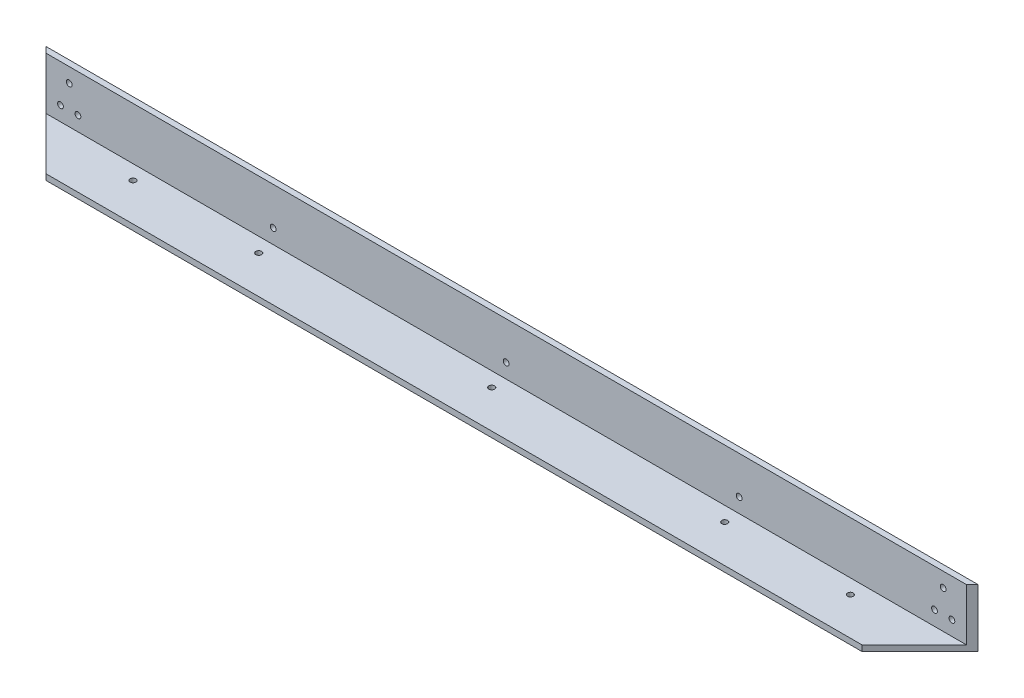
SolidWorks part; units mm, degrees
ref_plane "Front Plane" through (0, 0, 0) normal (0, 0, 1) x (1, 0, 0)
ref_plane "Top Plane" through (0, 0, 0) normal (0, 1, 0) x (1, 0, 0)
ref_plane "Right Plane" through (0, 0, 0) normal (1, 0, 0) x (0, 0, -1)
sketch "Sketch1" plane through (0, 0, 0) normal (1, 0, 0) x (0, 0, -1)
  line L0 (0, 0) -> (-31.75, 0)
  line L1 (-31.75, 0) -> (-31.75, 3.175)
  line L2 (-31.75, 3.175) -> (-3.175, 3.175)
  line L3 (-3.175, 3.175) -> (-3.175, 31.75)
  line L4 (-3.175, 31.75) -> (0, 31.75)
  line L5 (0, 31.75) -> (0, 0)
  dimension "LHeight" = 31.75
  dimension "LWidth" = 31.75
  dimension "LMaterialThickness" = 3.175
  dimension "D1" = 28.575
  dimension "D2" = 28.575
  dimension "D3" = 3.175
extrude "Boss-Extrude1" add sketch "Sketch1" along normal blind 510
chamfer "Chamfer6" distance 31.75 angle 45 1 edges at (510, 1.5875, 31.75)
chamfer "Chamfer7" distance 31.75 angle 45 1 edges at (0, 1.5875, 31.75)
sketch "TopHoles-Sketch3" plane through (0, 3.175, 0) normal (0, 1, 0) x (1, 0, 0)
  line L0 (510, 0) -> (0, 0) construction
  circle A9 centre (451.2625, -11.1125) radius 1.5875
  circle A10 centre (58.7375, -11.1125) radius 1.5875
  circle A13 centre (127.5, -11.1125) radius 1.5875
  circle A14 centre (255, -11.1125) radius 1.5875
  circle A15 centre (382.5, -11.1125) radius 1.5875
  dimension "D10" = 127.5
  dimension "D5" = 3.175
  dimension "D11" = 127.5
  dimension "D13" = 127.5
  dimension "D2" = 11.1125
  dimension "D3" = 58.7375
  dimension "D4" = 58.7375
extrude "TopHoles-Cut-Extrude2" cut sketch "TopHoles-Sketch3" against normal through all
sketch "FrontHoles-Sketch4" plane through (0, 0, 3.175) normal (0, 0, 1) x (1, 0, 0)
  line L0 (0, 0) -> (0, 31.75) construction
  line L1 (510, 0) -> (510, 31.75) construction
  line L3 (510, 31.75) -> (0, 31.75) construction
  line L7 (510, 0) -> (0, 0) construction
  circle A3 centre (494.125, 23.8125) radius 1.5875
  circle A4 centre (15.875, 23.8125) radius 1.5875
  circle A6 centre (11.1125, 11.1125) radius 1.5875
  circle A7 centre (20.6375, 11.1125) radius 1.5875
  circle A8 centre (489.3625, 11.1125) radius 1.5875
  circle A9 centre (498.8875, 11.1125) radius 1.5875
  circle A10 centre (127.5, 11.1125) radius 1.5875
  circle A11 centre (255, 11.1125) radius 1.5875
  circle A12 centre (382.5, 11.1125) radius 1.5875
  dimension "D2" = 3.175
  dimension "D7" = 11.1125
  dimension "D6" = 15.875
  dimension "D5" = 15.875
  dimension "D8" = 127.5
  dimension "D9" = 127.5
  dimension "D10" = 127.5
  dimension "D4" = 7.9375
  dimension "D11" = 11.1125
  dimension "D3" = 11.1125
  dimension "D12" = 20.6375
  dimension "D13" = 20.6375
extrude "FrontHoles-Cut-Extrude3" cut sketch "FrontHoles-Sketch4" against normal through all
equation "\"TopRailWidth\"= 1.25in"
equation "\"TopRailHeight\"= 1.25in"
equation "\"RailThickness\"= .125in'Spec"
equation "\"SideRailHoleY1FromEdge\"= \"HoleOffsetFromEdge\""
equation "\"SideRailHoleX1FromSide\"= \"HoleOffsetFromSide\""
equation "\"FrontBackRailLength\"= 510mm"
equation "\"VSWidth\"= 1.25in'Spec"
equation "\"HoleOffsetFromEdge\"= \"RailThickness\" * 2.5"
equation "\"HoleOffsetFromSide\"= \"RailThickness\" * 3.5"
equation "\"SideRailHoleX2FromSide\"= \"VSWidth\" - \"HoleOffsetFromEdge\" - \"RailThickness\"'Equals 20.6375"
equation "\"FasteningHoleDiameter\"= .125in"
equation "\"SideRailHoleY2FromSide\"= \"HoleOffsetFromSide\""
equation "\"LWidth@Sketch1\"=\"TopRailWidth\""
equation "\"LHeight@Sketch1\"=\"TopRailHeight\""
equation "\"LMaterialThickness@Sketch1\"=\"RailThickness\""
equation "\"D1@Boss-Extrude1\"= \"FrontBackRailLength\""
equation "\"D7@FrontHoles-Sketch4\"=\"SideRailHoleY2FromSide\""
equation "\"D1@Chamfer6\"=\"TopRailWidth\""
equation "\"D1@Chamfer7\"=\"TopRailWidth\""
equation "\"D6@FrontHoles-Sketch4\"=\"VSMidSideRailHoleXFromSideToCenter\" - \"RailThickness\""
equation "\"TopHoleY1FromSide\"= \"HoleOffsetFromSide\""
equation "\"TopCBLength\"= \"TopRailWidth\" * 2'Equals 63.5"
equation "\"FrontOrBackEnclosureOffsets\"= \"FrontBackRailLength\" / 4"
equation "\"D10@TopHoles-Sketch3\"=\"FrontOrBackEnclosureOffsets\""
equation "\"D11@TopHoles-Sketch3\"=\"FrontOrBackEnclosureOffsets\""
equation "\"D13@TopHoles-Sketch3\"=\"FrontOrBackEnclosureOffsets\""
equation "\"D8@FrontHoles-Sketch4\"=\"FrontOrBackEnclosureOffsets\""
equation "\"D9@FrontHoles-Sketch4\"=\"FrontOrBackEnclosureOffsets\""
equation "\"D10@FrontHoles-Sketch4\"=\"FrontOrBackEnclosureOffsets\""
equation "\"D4@FrontHoles-Sketch4\"=\"SideRailHoleY1FromEdge\""
equation "\"D11@FrontHoles-Sketch4\"=\"SideRailHoleX1FromSide\""
equation "\"D2@FrontHoles-Sketch4\"=\"FasteningHoleDiameter\""
equation "\"D3@FrontHoles-Sketch4\"=\"SideRailHoleX1FromSide\""
equation "\"D5@FrontHoles-Sketch4\"=\"VSMidSideRailHoleXFromSideToCenter\" - \"RailThickness\""
equation "\"D2@TopHoles-Sketch3\"=\"TopHoleY1FromSide\""
equation "\"D5@TopHoles-Sketch3\"=\"FasteningHoleDiameter\""
equation "\"FrontOrBackCornerEnclosureOffset\"= \"RailThickness\" + \"TopCBLength\" - \"HoleOffsetFromEdge\"'Equals 58.7375"
equation "\"D3@TopHoles-Sketch3\"=\"FrontOrBackCornerEnclosureOffset\""
equation "\"VSMidSideRailHoleXFromSideToCenter\"= \"RailThickness\" * 6"
equation "\"D12@FrontHoles-Sketch4\"=\"SideRailHoleX2FromSide\""
equation "\"D13@FrontHoles-Sketch4\"=\"SideRailHoleX2FromSide\""
